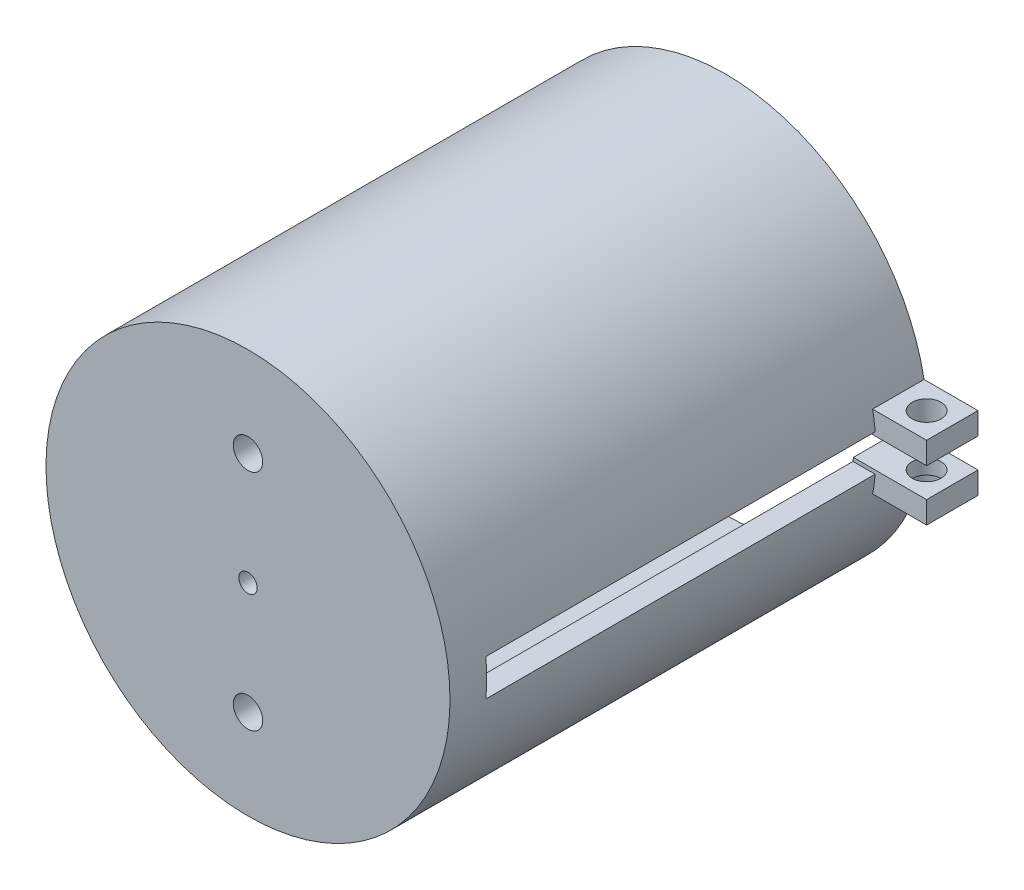
SolidWorks part; units mm, degrees
ref_plane "Front Plane" through (0, 0, 0) normal (0, 0, 1) x (1, 0, 0)
ref_plane "Top Plane" through (0, 0, 0) normal (0, 1, 0) x (1, 0, 0)
ref_plane "Right Plane" through (0, 0, 0) normal (1, 0, 0) x (0, 0, -1)
sketch "Sketch1" plane through (0, 0, 0) normal (0, 0, 1) x (1, 0, 0)
  line L0 (0, 23.495) -> (0, 15.24) construction
  line L1 (23.495, 0) -> (34.925, 0)
  line L2 (-23.495, 0) -> (-34.925, 0)
  line L3 (0, -15.24) -> (0, -23.495) construction
  circle A0 centre (0, 0) radius 23.495
  circle A1 centre (0, 0) radius 15.24
  circle A2 centre (0, 19.3675) radius 2.54
  circle A3 centre (0, -19.3675) radius 2.54
  circle A5 centre (0, 0) radius 34.925
  point P22 (0, 0)
  point P23 (0, 0)
  dimension "D1" = 8.255
  dimension "1.85" = 46.99
  dimension "D2" = 5.08
  dimension "D3" = 69.85
extrude "Boss-Extrude1" add sketch "Sketch1" along normal blind 6.35 contours A0 A3 A2 A1 | L1 A5 L2 A0 | L1 A0 L2 A5 region at (0, 24.2759, 0) region at (0, -22.8305, 0) region at (29.21, -0.7809, 0)
extrude "Boss-Extrude2" add sketch "Sketch1<2>" against normal blind 3.81 and the other way up to surface (6.35 mm away) contours A1 region at (0, 0, 0) other way up to face at (34.925, 0, 6.35)
sketch "Sketch1<2>" plane through (0, 0, 0) normal (0, 0, 1) x (1, 0, 0) same geometry as "Sketch1"
sketch "Sketch3" plane through (0, 0, 6.35) normal (0, 0, 1) x (1, 0, 0)
  circle A0 centre (0, 0) radius 1.5875
  dimension "D1" = 3.175
extrude "Cut-Extrude2" cut sketch "Sketch3" against normal through all
sketch "Sketch4" plane through (0, 0, 0) normal (0, 0, -1) x (-1, 0, 0)
  circle A0 centre (0, 0) radius 28.575
  circle A1 centre (0, 0) radius 34.925 construction
  circle A2 centre (0, 0) radius 34.925
  circle A3 centre (0, 0) radius 31.115
  circle M1 centre (0, 0) radius 34.925
  dimension "D1" = 57.15
  dimension "D2" = 3.81
extrude "Boss-Extrude3" add sketch "Sketch4" along normal blind 76.2 contours A3 M1 region at (33.9372, 0, 0)
sketch "Sketch5" plane through (0, 0, 0) normal (1, 0, 0) x (0, 0, -1)
  line L0 (76.2, -31.115) -> (76.2, 31.115) construction
  line L1 (76.2, 3.175) -> (0, 3.175)
  line L2 (76.2, 3.175) -> (76.2, -3.175)
  line L3 (76.2, -3.175) -> (0, -3.175)
  line L4 (0, 3.175) -> (0, -3.175)
  dimension "D1" = 6.35
extrude "Cut-Extrude3" cut sketch "Sketch5" along normal through all from offset 30.48
sketch "Sketch6" plane through (0, 0, 0) normal (0, 1, 0) x (1, 0, 0)
  line L1 (34.7804, 76.2) -> (43.6704, 76.2)
  line L2 (34.7804, 76.2) -> (34.7804, 67.31)
  line L3 (34.7804, 67.31) -> (43.6704, 67.31)
  line L4 (43.6704, 76.2) -> (43.6704, 67.31)
  circle A0 centre (39.2254, 71.755) radius 2.5
  dimension "D3" = 5
  dimension "D1" = 8.89
  dimension "D2" = 8.89
  dimension "D4" = 4.445
  dimension "D5" = 4.445
extrude "Boss-Extrude4" add sketch "Sketch6" along normal blind 3.81 from offset 2.54 separate body
extrude "Boss-Extrude5" add sketch "Sketch6<2>" against normal blind 3.81 from offset 2.54 separate body offset against normal yes
sketch "Sketch6<2>" plane through (0, 0, 0) normal (0, 1, 0) x (1, 0, 0) same geometry as "Sketch6"
sketch "Sketch8" plane through (34.7804, 0, 0) normal (-1, 0, 0) x (0, 0, 1)
  line L0 (-67.31, -2.54) -> (-76.2, -2.54) construction
  line L1 (-76.2, -2.54) -> (-76.2, -6.35) construction
  line L2 (-76.2, -6.35) -> (-67.31, -6.35) construction
  line L3 (-67.31, -6.35) -> (-67.31, -2.54) construction
  line L4 (-76.2, 2.54) -> (-67.31, 2.54) construction
  line L5 (-67.31, 2.54) -> (-67.31, 6.35) construction
  line L6 (-67.31, 6.35) -> (-76.2, 6.35) construction
  line L7 (-76.2, 6.35) -> (-76.2, 2.54) construction
  line L8 (-67.31, -2.54) -> (-76.2, -2.54)
  line L9 (-76.2, -2.54) -> (-76.2, -6.35)
  line L10 (-76.2, -6.35) -> (-67.31, -6.35)
  line L11 (-67.31, -6.35) -> (-67.31, -2.54)
  line L12 (-76.2, 2.54) -> (-67.31, 2.54)
  line L13 (-67.31, 2.54) -> (-67.31, 6.35)
  line L14 (-67.31, 6.35) -> (-76.2, 6.35)
  line L15 (-76.2, 6.35) -> (-76.2, 2.54)
extrude "Boss-Extrude6" add sketch "Sketch8" along normal up to surface (4.3202 mm away) up to face at (-0.0812, 0, -38.1)
sketch "Sketch9" plane through (0, -6.35, 0) normal (0, -1, 0) x (1, 0, 0)
  circle A0 centre (39.2254, -71.755) radius 2.5 construction
  circle A1 centre (39.2254, -71.755) radius 2.5
  circle A2 centre (39.2254, -71.755) radius 3
  dimension "D1" = 6
extrude "Cut-Extrude4" cut sketch "Sketch9" against normal blind 1.27
